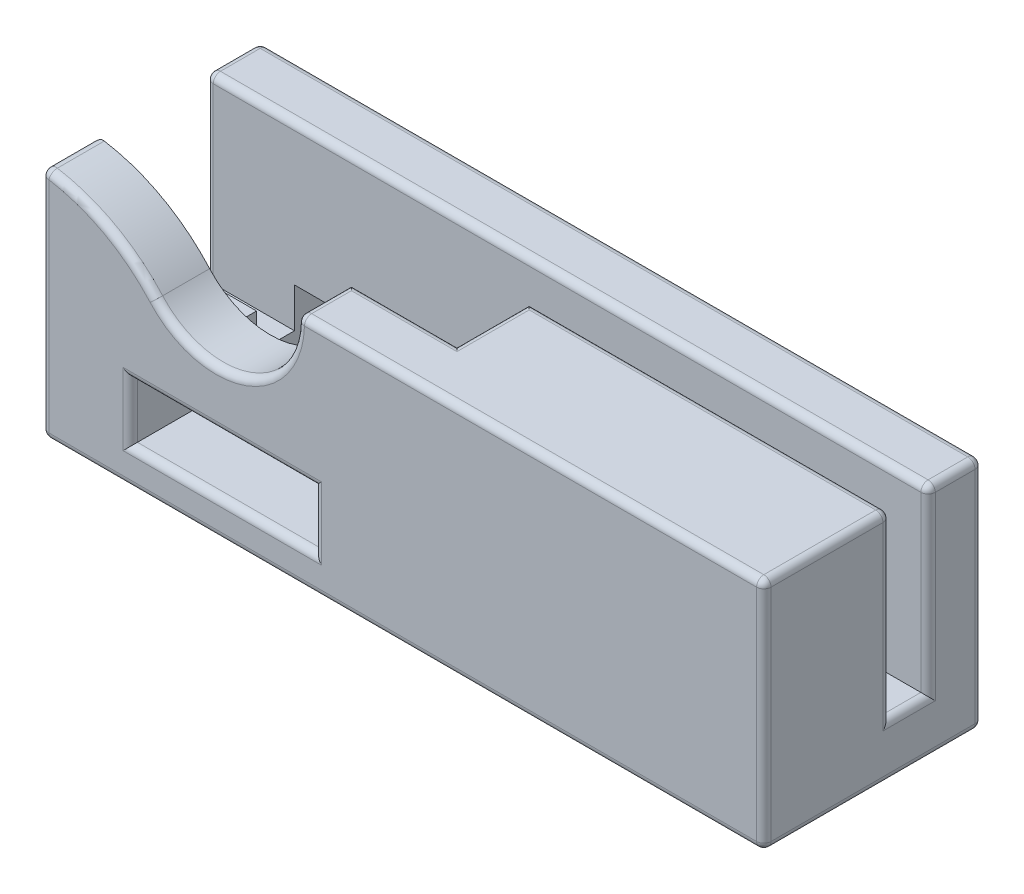
SolidWorks part; units mm, degrees
ref_plane "Front Plane" through (0, 0, 0) normal (0, 0, 1) x (1, 0, 0)
ref_plane "Top Plane" through (0, 0, 0) normal (0, 1, 0) x (1, 0, 0)
ref_plane "Right Plane" through (0, 0, 0) normal (1, 0, 0) x (0, 0, -1)
sketch "Sketch1" plane through (0, 0, 0) normal (0, 1, 0) x (1, 0, 0)
  line L1 (0, 0) -> (40, 0)
  line L2 (0, 0) -> (0, -12.1)
  line L3 (0, -12.1) -> (40, -12.1)
  line L4 (40, 0) -> (40, -12.1)
  dimension "D1" = 12.1
  dimension "D2" = 40
extrude "Boss-Extrude1" add sketch "Sketch1" along normal blind 3
sketch "Sketch2" plane through (0, 3, 0) normal (0, 1, 0) x (1, 0, 0)
  line L0 (40, -12.1) -> (40, 0) construction
  line L1 (0, 0) -> (40, 0)
  line L2 (0, 0) -> (0, -3)
  line L3 (0, -3) -> (40, -3)
  line L4 (40, 0) -> (40, -3)
  line L6 (0, -12.1) -> (40, -12.1)
  line L7 (0, -12.1) -> (0, -5.1)
  line L8 (0, -5.1) -> (40, -5.1)
  line L9 (40, -12.1) -> (40, -5.1)
  dimension "D1" = 3
  dimension "D2" = 7
extrude "Boss-Extrude2" add sketch "Sketch2" along normal blind 10
sketch "Sketch3" plane through (0, 0, 0) normal (0, 0, -1) x (-1, 0, 0)
  line L0 (-40, 0) -> (0, 0) construction
  line L1 (-15.1, 5.2) -> (-4.9, 5.2)
  line L2 (-15.1, 5.2) -> (-15.1, 2)
  line L3 (-15.1, 2) -> (-4.9, 2)
  line L4 (-4.9, 5.2) -> (-4.9, 2)
  point P4 (-10, 2)
  point P7 (-20, 0)
  dimension "D1" = 3.2
  dimension "D2" = 10.2
  dimension "D3" = 10
  dimension "D4" = 2
extrude "Cut-Extrude1" cut sketch "Sketch3" against normal through all
sketch "Sketch4" plane through (0, 0, 0) normal (-1, 0, 0) x (0, 0, 1)
  line L1 (5.1, 13) -> (9.1, 13)
  line L2 (5.1, 13) -> (5.1, 5)
  line L3 (5.1, 5) -> (9.1, 5)
  line L4 (9.1, 13) -> (9.1, 5)
  dimension "D1" = 4
  dimension "D2" = 8
extrude "Cut-Extrude2" cut sketch "Sketch4" against normal blind 20
sketch "Sketch5" plane through (0, 0, 12.1) normal (0, 0, 1) x (1, 0, 0)
  circle A0 centre (9.6557, 12.73) radius 4.5
  dimension "D1" = 9
extrude "Cut-Extrude3" cut sketch "Sketch5" against normal blind 3
fillet "Fillet2" radius 10 1 edges at (5.1639, 13, 10.6)
fillet "Fillet1" radius 0.4 37 edges at (30, 13, 5.1) (20, 13, 3) (40, 13, 8.6) (40, 8, 5.1) (40, 3, 4.05) (40, 8, 3) (40, 13, 1.5) (0, 13, 1.5) (0, 8, 3) (0, 3, 4.05) (0, 4, 5.1) (40, 6.5, 0) (20, 13, 0) (0, 6.5, 0) (4.9, 3.6, 0) (10, 5.2, 0) (15.1, 3.6, 0) (10, 2, 0) (40, 0, 6.05) (20, 0, 0) (0, 0, 6.05) (0, 6.5, 12.1) (27.0738, 13, 12.1) (40, 6.5, 12.1) (20, 0, 12.1) (4.9, 3.6, 12.1) (10, 2, 12.1) (15.1, 3.6, 12.1) (10, 5.2, 12.1) (0, 5, 7.1) (0, 9, 9.1) (11.3862, 8.576, 12.1) (20, 13, 7.1) (14.1476, 13, 10.6) (17.0738, 13, 9.1) (0, 13, 10.6) (3.4501, 11.9434, 12.1)
